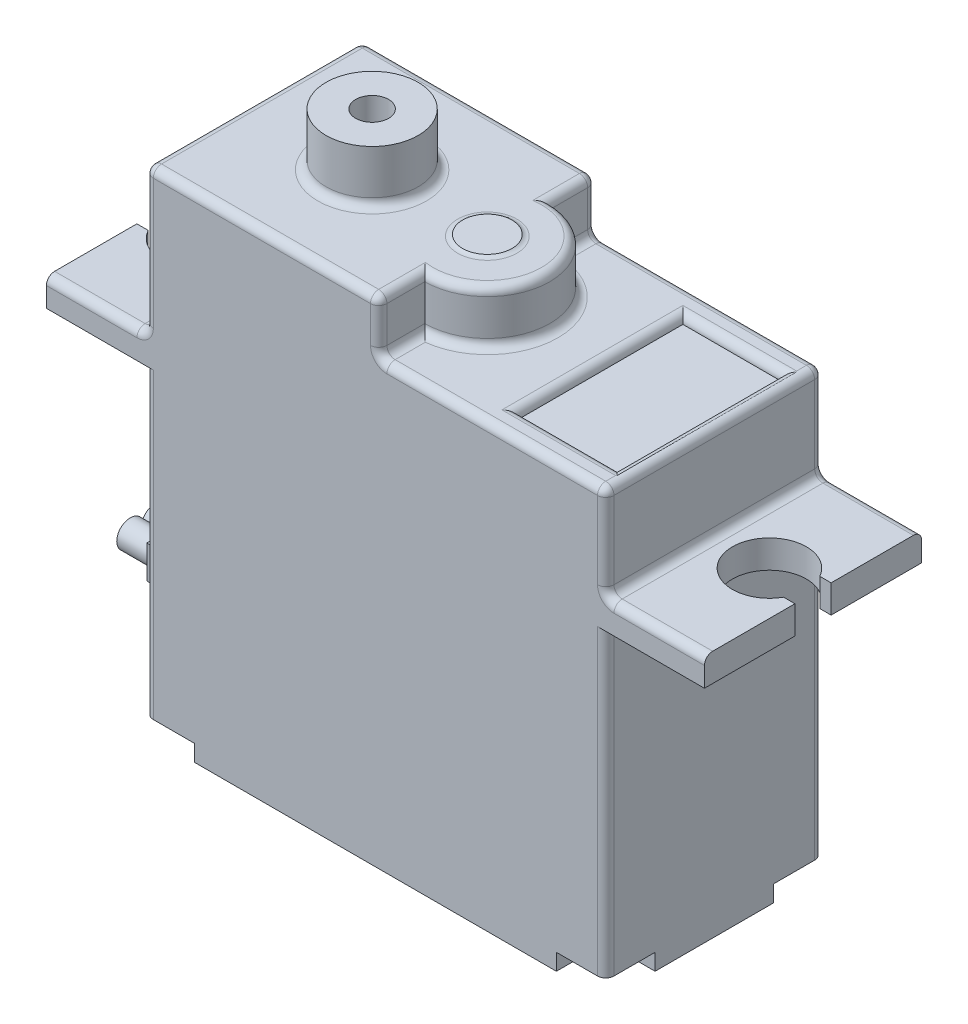
SolidWorks part; units mm, degrees
ref_plane "Ön Düzlem" through (0, 0, 0) normal (0, 0, 1) x (1, 0, 0)
ref_plane "Üst Düzlem" through (0, 0, 0) normal (0, 1, 0) x (1, 0, 0)
ref_plane "Sağ Düzlem" through (0, 0, 0) normal (1, 0, 0) x (0, 0, -1)
sketch "Çizim1" plane through (0, 0, 0) normal (0, 1, 0) x (1, 0, 0)
  line L1 (0, 0) -> (28, 0)
  line L2 (0, 0) -> (0, 13.2)
  line L3 (0, 13.2) -> (28, 13.2)
  line L4 (28, 0) -> (28, 13.2)
  dimension "D1" = 28
  dimension "D2" = 13.2
extrude "Yükseklik-Ekstrüzyon1" add sketch "Çizim1" along normal blind 26.8
sketch "Çizim2" plane through (0, 0, 0) normal (0, -1, 0) x (1, 0, 0)
  line L0 (0, -6.6) -> (28, -6.6) construction
  line L1 (0, -13.2) -> (0, 0) construction
  line L2 (28, 0) -> (28, -13.2) construction
  line L3 (14, 0) -> (14, -13.2) construction
  line L4 (0, 0) -> (28, 0) construction
  line L5 (28, -13.2) -> (0, -13.2) construction
  line L6 (25, 0) -> (25, -3)
  line L7 (0, 0) -> (3, 0)
  line L8 (0, 0) -> (0, -3)
  line L9 (0, -3) -> (3, -3)
  line L10 (3, 0) -> (3, -3)
  line L11 (28, -3) -> (25, -3)
  line L12 (28, 0) -> (28, -3)
  line L13 (28, 0) -> (25, 0)
  line L14 (28, -13.2) -> (25, -13.2)
  line L15 (28, -13.2) -> (28, -10.2)
  line L16 (28, -10.2) -> (25, -10.2)
  line L17 (25, -13.2) -> (25, -10.2)
  line L18 (3, -13.2) -> (3, -10.2)
  line L19 (0, -10.2) -> (3, -10.2)
  line L20 (0, -13.2) -> (0, -10.2)
  line L21 (0, -13.2) -> (3, -13.2)
  dimension "D1" = 3
  dimension "D2" = 3
extrude "Kes-Ekstrüzyon1" cut sketch "Çizim2" against normal blind 1
fillet "Radyus1" radius 1 4 edges at (25, 0.5, -10.2) (25, 0.5, -3) (3, 0.5, -10.2) (3, 0.5, -3)
sketch "Çizim3" plane through (0, 0, 0) normal (-1, 0, 0) x (0, 0, 1)
  line L0 (-10.2, 0) -> (-3, 0) construction
  line L1 (-9.85, 7) -> (-3.35, 7)
  line L2 (-9.85, 7) -> (-9.85, 3)
  line L3 (-9.85, 3) -> (-3.35, 3)
  line L4 (-3.35, 7) -> (-3.35, 3)
  line L6 (-6.6, 0) -> (-6.6, 23.2713) construction
  dimension "D1" = 7
  dimension "D2" = 6.5
  dimension "D3" = 4
  dimension "D4" = 3.25
extrude "Yükseklik-Ekstrüzyon2" add sketch "Çizim3" along normal blind 4
fillet "Radyus2" radius 1 4 edges at (-2, 3, -3.35) (-2, 7, -3.35) (-2, 3, -9.85) (-2, 7, -9.85)
sketch "Çizim4" plane through (0, 0, 0) normal (-1, 0, 0) x (0, 0, 1)
  line L0 (-13.2, 26.8) -> (-13.2, 1) construction
  line L1 (-13.2, 21.1) -> (0, 21.1)
  line L2 (-13.2, 21.1) -> (-13.2, 19.4)
  line L3 (-13.2, 19.4) -> (0, 19.4)
  line L4 (0, 21.1) -> (0, 19.4)
  line L5 (0, 26.8) -> (0, 1) construction
  line L7 (-10.2, 0) -> (-3, 0) construction
  dimension "D1" = 1.7
  dimension "D2" = 19.4
extrude "Yükseklik-Ekstrüzyon3" add sketch "Çizim4" along normal blind 6
sketch "Çizim5" plane through (28, 0, 0) normal (1, 0, 0) x (0, 0, -1)
  line L0 (0, 26.8) -> (0, 1) construction
  line L1 (0, 21.1) -> (13.2, 21.1)
  line L2 (0, 21.1) -> (0, 19.4)
  line L3 (0, 19.4) -> (13.2, 19.4)
  line L4 (13.2, 21.1) -> (13.2, 19.4)
  line L5 (0, 26.8) -> (0, 21.1) construction
  line L6 (13.2, 26.8) -> (13.2, 1) construction
  line L8 (3, 0) -> (10.2, 0) construction
  dimension "D1" = 1.7
  dimension "D2" = 19.4
extrude "Yükseklik-Ekstrüzyon4" add sketch "Çizim5" along normal blind 6
fillet "Radyus3" radius 0.5 4 edges at (0, 10.2, -13.2) (0, 10.2, 0)
sketch "Çizim6" plane through (0, 21.1, 0) normal (0, 1, 0) x (1, 0, 0)
  line L0 (-6, 0) -> (-6, 13.2) construction
  line L1 (-6, 7.7) -> (-5.3128, 7.7)
  line L2 (-6, 7.7) -> (-6, 5.5)
  line L3 (-6, 5.5) -> (-5.3128, 5.5)
  line L4 (14, 13.2) -> (14, 0) construction
  line L5 (-6, 0) -> (0, 0) construction
  line L6 (-6, 13.2) -> (0, 13.2) construction
  line L9 (0, 6.6) -> (-6.7, 6.6) construction
  line L11 (0, 0) -> (0, 13.2) construction
  line L12 (28, 13.2) -> (0, 13.2) construction
  line L13 (0, 0) -> (28, 0) construction
  line L14 (28, 6.6) -> (34.7, 6.6) construction
  line L15 (34, 5.5) -> (33.3128, 5.5)
  line L16 (34, 7.7) -> (34, 5.5)
  line L17 (34, 7.7) -> (33.3128, 7.7)
  arc A0 (-5.3128, 5.5) -> (-5.3128, 7.7) centre (-3.35, 6.6) ccw
  arc A1 (33.3128, 5.5) -> (33.3128, 7.7) centre (31.35, 6.6) cw
  dimension "D1" = 5.5
  dimension "D2" = 5.5
extrude "Kes-Ekstrüzyon3" cut sketch "Çizim6" against normal blind 2
sketch "Çizim7" plane through (0, 26.8, 0) normal (0, 1, 0) x (1, 0, 0)
  line L0 (0, 0) -> (28, 0) construction
  line L1 (0, 13.2) -> (14.2, 13.2)
  line L2 (0, 13.2) -> (0, 0)
  line L3 (0, 0) -> (14.2, 0)
  line L4 (14.2, 13.2) -> (14.2, 10.4)
  line L5 (0, 6.6) -> (28, 6.6) construction
  line L6 (28, 0) -> (28, 13.2) construction
  line L7 (14.2, 2.8) -> (14.2, 0)
  arc A0 (14.2, 2.8) -> (14.2, 10.4) centre (14.2, 6.6) ccw
  dimension "D2" = 7.6
  dimension "D1" = 14.2
extrude "Yükseklik-Ekstrüzyon6" add sketch "Çizim7" along normal blind 3.2
sketch "Çizim8" plane through (0, 30, 0) normal (0, 1, 0) x (1, 0, 0)
  circle A0 centre (14.2, 6.6) radius 1.5
extrude "Yükseklik-Ekstrüzyon7" add sketch "Çizim8" along normal blind 0.1
sketch "Çizim9" plane through (0, 30, 0) normal (0, 1, 0) x (1, 0, 0)
  line L0 (0, 6.6) -> (28, 6.6) construction
  line L1 (0, 0) -> (0, 13.2) construction
  line L2 (28, 13.2) -> (28, 0) construction
  line L3 (0, 13.2) -> (0, 0) construction
  circle A0 centre (7.2, 6.6) radius 2.8
  circle A1 centre (7.2, 6.6) radius 1
  dimension "D1" = 7.2
extrude "Yükseklik-Ekstrüzyon8" add sketch "Çizim9" along normal blind 3.2
sketch "Çizim11" plane through (0, 26.8, 0) normal (0, 1, 0) x (1, 0, 0)
  line L0 (28, 6.6) -> (19.7116, 6.6) construction
  line L1 (27.0896, 11.6) -> (21.0896, 11.6)
  line L2 (27.0896, 11.6) -> (27.0896, 1.6)
  line L3 (27.0896, 1.6) -> (21.0896, 1.6)
  line L4 (21.0896, 11.6) -> (21.0896, 1.6)
  line L5 (28, 13.2) -> (28, 0) construction
  dimension "D1" = 10
  dimension "D2" = 6
  dimension "D3" = 5
extrude "Kes-Ekstrüzyon7" cut sketch "Çizim11" against normal blind 0.5
fillet "Radyus4" radius 0.5 30 edges at (-3, 21.1, -13.2) (-3, 21.1, 0) (28, 26.8, -6.6) (18, 26.8, -6.6) (21.0896, 26.8, -6.6) (24.0896, 26.8, -1.6) (27.0896, 26.8, -6.6) (24.0896, 26.8, -11.6) (0, 25.55, -13.2) (0, 25.55, 0) (0, 21.1, -6.6) (7.2, 30, -3.8) (14.2, 30, -5.1) (7.1, 30, -13.2) (14.2, 30, -11.8) (18, 30, -6.6) (14.2, 30, -1.4) (7.1, 30, 0) (0, 30, -6.6)
sketch "Çizim14" plane through (-4, 0, 0) normal (-1, 0, 0) x (0, 0, 1)
  line L0 (-9.85, 5) -> (-3.35, 5) construction
  line L1 (-9.85, 6) -> (-9.85, 4) construction
  line L2 (-3.35, 4) -> (-3.35, 6) construction
  line L3 (-6.6, 7) -> (-6.6, 3) construction
  line L4 (-4.35, 7) -> (-8.85, 7) construction
  line L5 (-8.85, 3) -> (-4.35, 3) construction
  line L7 (-9.1, 6) -> (-4.1, 6)
  line L8 (-9.1, 6) -> (-9.1, 4)
  line L9 (-9.1, 4) -> (-4.1, 4)
  line L10 (-4.1, 6) -> (-4.1, 4)
  line L11 (-10.7188, 7.8648) -> (-2.4417, 7.8648)
  line L12 (-10.7188, 7.8648) -> (-10.7188, 2.1185)
  line L13 (-10.7188, 2.1185) -> (-2.4417, 2.1185)
  line L14 (-2.4417, 7.8648) -> (-2.4417, 2.1185)
  dimension "D1" = 2.5
  dimension "D2" = 5
  dimension "D3" = 2
  dimension "D4" = 1
extrude "Kes-Ekstrüzyon8" cut sketch "Çizim14" against normal blind 3
sketch "Çizim15" plane through (-4, 0, 0) normal (-1, 0, 0) x (0, 0, 1)
  line L0 (-9.1, 5) -> (-4.1, 5) construction
  line L1 (-9.1, 6) -> (-9.1, 4) construction
  line L2 (-4.1, 4) -> (-4.1, 6) construction
  line L3 (-6.6, 6) -> (-6.6, 4) construction
  line L4 (-4.1, 6) -> (-9.1, 6) construction
  line L5 (-9.1, 4) -> (-4.1, 4) construction
  arc A0 (-7.35, 4.6563) -> (-5.85, 4.6563) centre (-6.6, 5) ccw
  arc A1 (-5.85, 4.6563) -> (-5.85, 5.3437) centre (-5.1, 5) ccw
  arc A2 (-7.35, 5.3437) -> (-7.35, 4.6563) centre (-8.1, 5) ccw
  arc A3 (-5.85, 5.3437) -> (-7.35, 5.3437) centre (-6.6, 5) ccw
  dimension "D1" = 1.65
  dimension "D2" = 1.65
  dimension "D4" = 1.65
  dimension "D3" = 1.5
  dimension "D5" = 1.5
extrude "Yükseklik-Ekstrüzyon9" add sketch "Çizim15" along normal blind 2
sketch "Çizim17" plane through (-6, 0, 0) normal (-1, 0, 0) x (0, 0, 1)
  circle A0 centre (-8.1, 5) radius 0.4
  circle A1 centre (-6.6, 5) radius 0.4
  circle A2 centre (-5.1, 5) radius 0.4
extrude "Yükseklik-Ekstrüzyon10" add sketch "Çizim17" along normal blind 0.1
